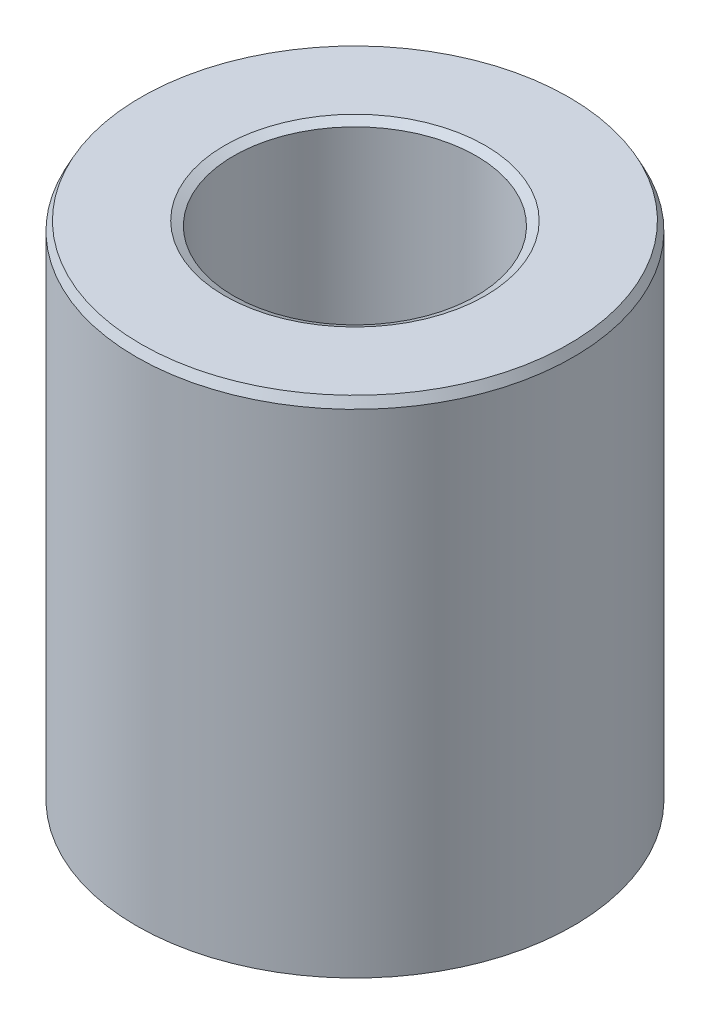
SolidWorks part; units mm, degrees
ref_plane "Front Plane" through (0, 0, 0) normal (0, 0, 1) x (1, 0, 0)
ref_plane "Top Plane" through (0, 0, 0) normal (0, 1, 0) x (1, 0, 0)
ref_plane "Right Plane" through (0, 0, 0) normal (1, 0, 0) x (0, 0, -1)
sketch "Sketch1" plane through (0, 0, 0) normal (0, 1, 0) x (1, 0, 0)
  circle A0 centre (0, 0) radius 30
  dimension "SLEEVE_OD" = 60
extrude "Boss-Extrude1" add sketch "Sketch1" along normal blind 69.4828
sketch "Sketch2" plane through (0, 0, 0) normal (0, 1, 0) x (1, 0, 0)
  circle A0 centre (0, 0) radius 16.6612
  dimension "BORE_D" = 33.3225
extrude "Cut-Extrude1" cut sketch "Sketch2" along normal through all
chamfer "Chamfer1" distance 1.2294 angle 26.979 4 edges at (0, 69.4828, 16.6612) (0, 0, 16.6612) (0, 0, 30) (0, 69.4828, 30) first distance on face at (0, 69.4828, 16.6612) first distance on face at (0, 0, 16.6612) first distance on face at (0, 69.4828, 30)
